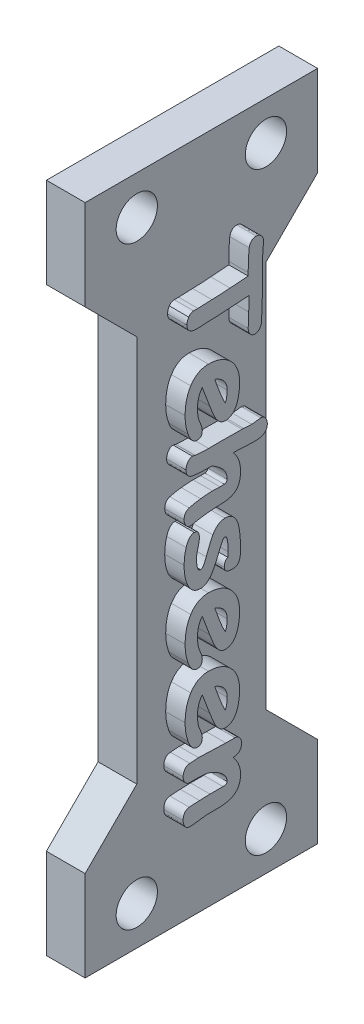
SolidWorks part; units mm, degrees
ref_plane "Front Plane" through (0, 0, 0) normal (0, 0, 1) x (1, 0, 0)
ref_plane "Top Plane" through (0, 0, 0) normal (0, 1, 0) x (1, 0, 0)
ref_plane "Right Plane" through (0, 0, 0) normal (1, 0, 0) x (0, 0, -1)
ref_plane "Plane1" through (120.9887, 0, 0) normal (-1, 0, 0) x (0, -1, 0)
sketch "Sketch1" plane through (120.9887, 0, 0) normal (-1, 0, 0) x (0, -1, 0)
  line L126 (75.0051, 19) -> (75.0051, 37)
  line L127 (75.0051, 37) -> (23.0051, 37)
  line L128 (23.0051, 37) -> (23.0051, 19)
  line L129 (23.0051, 19) -> (75.0051, 19)
  circle A0 centre (26.0051, 33) radius 1.5995
  circle A1 centre (26.0051, 23) radius 1.5995
  circle A2 centre (72.0051, 33) radius 1.5995
  circle A3 centre (72.0051, 23) radius 1.5995
  dimension "D1" = 3.199
  dimension "D2" = 23.0051
  dimension "D3" = 26.0051
  dimension "D4" = 72.0051
  dimension "D5" = 75.0051
  dimension "D6" = 19
  dimension "D7" = 23
  dimension "D8" = 33
  dimension "D9" = 37
extrude "Boss-Extrude1" add sketch "Sketch1" against normal blind 3
sketch "Sketch2" plane through (120.9887, 0, 0) normal (-1, 0, 0) x (0, 0, 1)
  line L0 (28, -23.0051) -> (28, -75.0051) construction
  line L1 (37, -34.0051) -> (33, -34.0051)
  line L2 (37, -34.0051) -> (37, -64.0051)
  line L3 (37, -64.0051) -> (33, -64.0051)
  line L4 (33, -34.0051) -> (33, -64.0051)
  line L5 (37, -23.0051) -> (19, -23.0051) construction
  line L6 (19, -75.0051) -> (37, -75.0051) construction
  line L7 (37, -75.0051) -> (37, -23.0051) construction
  line L8 (33, -34.0051) -> (37, -30.0051)
  line L9 (33, -64.0051) -> (37, -68.0051)
  line L10 (37, -68.0051) -> (37, -64.0051)
  line L11 (37, -30.0051) -> (37, -34.0051)
  line L12 (19, -30.0051) -> (19, -34.0051)
  line L13 (19, -68.0051) -> (19, -64.0051)
  line L14 (23, -64.0051) -> (19, -68.0051)
  line L15 (23, -34.0051) -> (19, -30.0051)
  line L16 (23, -34.0051) -> (23, -64.0051)
  line L17 (19, -64.0051) -> (23, -64.0051)
  line L18 (19, -34.0051) -> (19, -64.0051)
  line L19 (19, -34.0051) -> (23, -34.0051)
  point P10 (37, -49.0051)
  point P13 (37, -49.0051)
  line M10 (19, -23.0051) -> (19, -75.0051)
  line M12 (37, -75.0051) -> (37, -23.0051)
  dimension "D1" = 30
  dimension "D2" = 4
extrude "Cut-Extrude1" cut sketch "Sketch2" against normal through all contours L1 L4 L3 M12 | L8 L1 M12 | L19 L15 M10 | L19 L17 L16 M10 | L17 L14 M10 | L3 L9 M12 region at (120.9887, -49.0051, 35) region at (120.9887, -32.6718, 35.6667) region at (120.9887, -65.3385, 35.6667) region at (120.9887, -32.6718, 20.3333) region at (120.9887, -49.0051, 21) region at (120.9887, -65.3385, 20.3333)
sketch "Sketch3" plane through (123.9887, 0, 0) normal (1, 0, 0) x (0, 0, -1)
  line L0 (-30.6154, -23.0051) -> (-30.6154, -75.0051) construction
  text T0 "Tehseen" font "Comic Sans MS" height 6
extrude "Boss-Extrude2" add sketch "Sketch3" along normal blind 1.5
